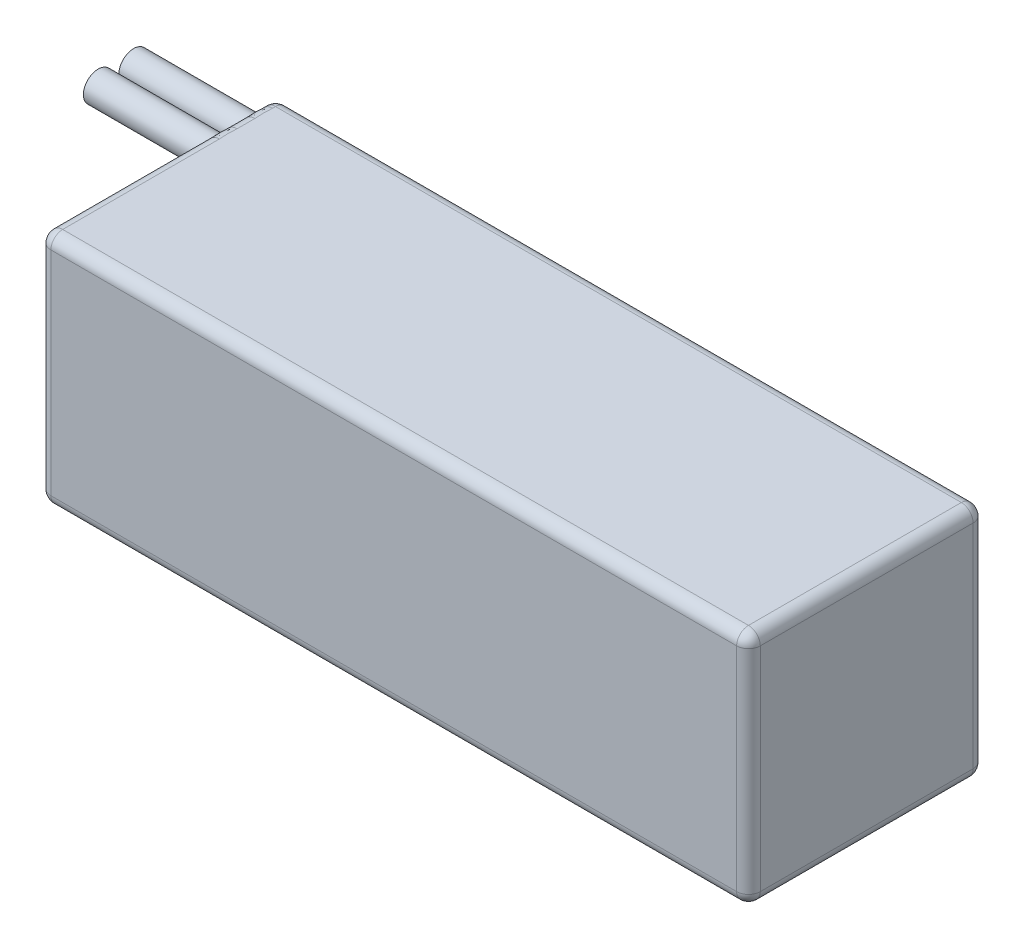
SolidWorks part; units mm, degrees
material "VITON"
ref_plane "Front Plane" through (0, 0, 0) normal (0, 0, 1) x (1, 0, 0)
ref_plane "Top Plane" through (0, 0, 0) normal (0, 1, 0) x (1, 0, 0)
ref_plane "Right Plane" through (0, 0, 0) normal (1, 0, 0) x (0, 0, -1)
sketch "Sketch1" plane through (0, 0, 0) normal (0, 0, 1) x (1, 0, 0)
  line L1 (0, 0) -> (152.4, 0)
  line L2 (0, 0) -> (0, 50.8)
  line L3 (0, 50.8) -> (152.4, 50.8)
  line L4 (152.4, 0) -> (152.4, 50.8)
  dimension "D1" = 152.4
  dimension "D2" = 50.8
extrude "Boss-Extrude1" add sketch "Sketch1" along normal blind 50.8
sketch "Sketch2" plane through (0, 0, 0) normal (-1, 0, 0) x (0, 0, 1)
  line L0 (50.8, 50.8) -> (0, 50.8) construction
  line L1 (0, 50.8) -> (0, 0) construction
  circle A0 centre (5.08, 45.72) radius 3.175
  circle A1 centre (12.7, 45.72) radius 3.175
  dimension "D2" = 6.35
  dimension "D3" = 6.35
  dimension "D1" = 7.62
  dimension "D4" = 5.08
  dimension "D5" = 5.08
extrude "Boss-Extrude2" add sketch "Sketch2" along normal blind 25.4
fillet "Fillet1" radius 2.54 12 edges at (0, 25.4, 0) (0, 0, 25.4) (76.2, 0, 0) (152.4, 0, 25.4) (152.4, 25.4, 0) (152.4, 25.4, 50.8) (76.2, 0, 50.8) (0, 25.4, 50.8) (152.4, 50.8, 25.4) (76.2, 50.8, 50.8) (0, 50.8, 25.4) (76.2, 50.8, 0)
